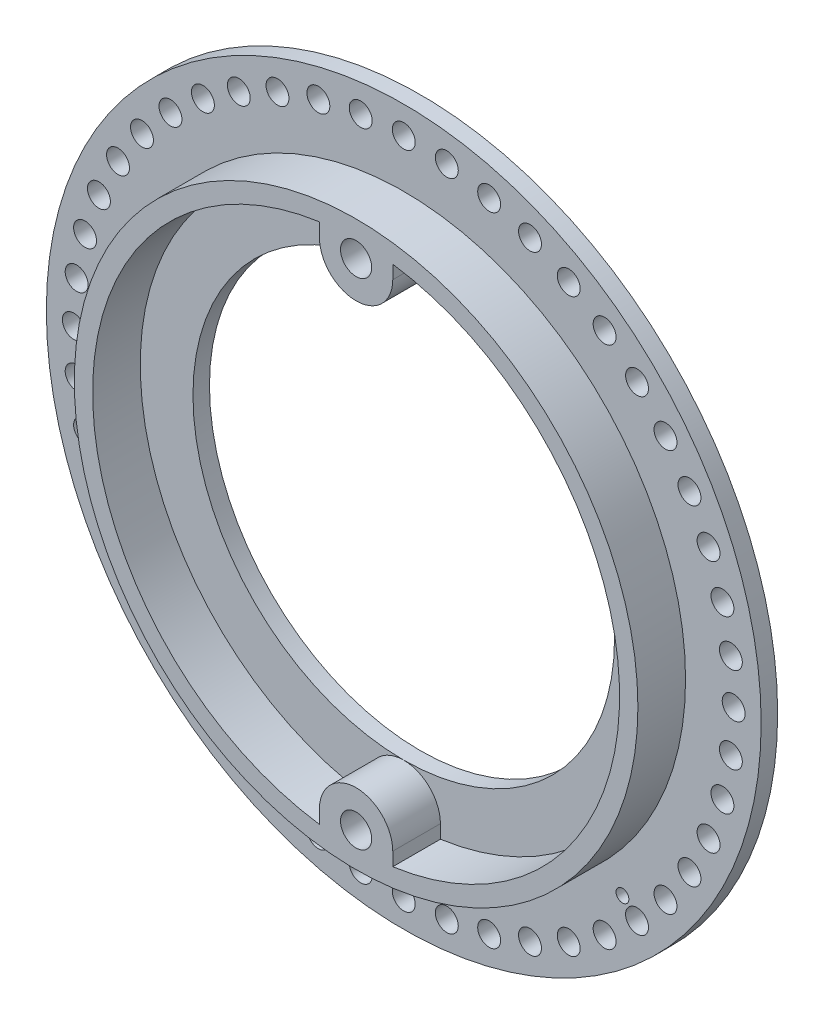
SolidWorks part; units mm, degrees
ref_plane "Front Plane" through (0, 0, 0) normal (0, 0, 1) x (1, 0, 0)
ref_plane "Top Plane" through (0, 0, 0) normal (0, 1, 0) x (1, 0, 0)
ref_plane "Right Plane" through (0, 0, 0) normal (1, 0, 0) x (0, 0, -1)
sketch "Sketch1" plane through (0, 0, 0) normal (0, 0, 1) x (1, 0, 0)
  circle A0 centre (0, 0) radius 39
  dimension "D1" = 78
extrude "Boss-Extrude1" add sketch "Sketch1" along normal blind 1.8
sketch "Sketch3" plane through (0, 0, 1.8) normal (0, 0, 1) x (1, 0, 0)
  line L0 (-4, 27) -> (-4, 28.4704)
  line L1 (4, 27) -> (4, 28.4704)
  line L2 (4, -27) -> (4, -28.4704)
  line L3 (-4, -27) -> (-4, -28.4704)
  circle A0 centre (0, 0) radius 30.75
  arc A1 (-4, 28.4704) -> (-4, -28.4704) centre (0, 0) ccw
  arc A2 (-4, 27) -> (4, 27) centre (0, 27) ccw
  circle A3 centre (0, 0) radius 28.75 construction
  arc A4 (4, -27) -> (-4, -27) centre (0, -27) ccw
  arc A5 (4, -28.4704) -> (4, 28.4704) centre (0, 0) ccw
  point P18 (0, 0)
  point P22 (-0.2453, 0)
  dimension "D1" = 61.5
  dimension "D3" = 8
  dimension "D5" = 2
  dimension "D4" = 27
  dimension "D2" = 2
extrude "Boss-Extrude2" add sketch "Sketch3" along normal blind 5.2 contours A1 L3 A4 L2 A5 L1 A2 L0 | A0
sketch "Sketch5" plane through (0, 0, 7) normal (0, 0, 1) x (1, 0, 0)
  circle A0 centre (0, -27) radius 1.7
  circle A1 centre (0, 27) radius 1.7
  point P7 (0, 0)
  dimension "D1" = 27
  dimension "D2" = 3.4
  dimension "D3" = 2
  dimension "D4" = 54
extrude "Cut-Extrude2" cut sketch "Sketch5" against normal up to surface (7 mm away) up to face at (39, 0, 0)
sketch "Sketch6" plane through (0, 0, 0) normal (0, 0, -1) x (-1, 0, 0)
  circle A0 centre (0, 27) radius 3
  circle A1 centre (0, -27) radius 3
  dimension "D1" = 6
  dimension "D2" = 6
  dimension "D3" = 27
  dimension "D4" = 27
extrude "Cut-Extrude3" cut sketch "Sketch6" against normal blind 4.5
sketch "Sketch7" plane through (0, 0, 0) normal (0, 0, -1) x (-1, 0, 0)
  circle A0 centre (0, 0) radius 23
  dimension "D1" = 46
extrude "Cut-Extrude4" cut sketch "Sketch7" against normal up to surface (1.8 mm away) up to face at (0, 0, 1.8)
sketch "Sketch8" plane through (0, 0, 1.8) normal (0, 0, 1) x (1, 0, 0)
  circle A0 centre (36, 0) radius 1.25
  circle A1 centre (35.692, -4.6989) radius 1.25
  circle A2 centre (34.7733, -9.3175) radius 1.25
  circle A3 centre (33.2597, -13.7766) radius 1.25
  circle A4 centre (31.1769, -18) radius 1.25
  circle A5 centre (28.5607, -21.9154) radius 1.25
  circle A6 centre (25.4558, -25.4558) radius 1.25
  circle A7 centre (21.9154, -28.5607) radius 1.25
  circle A8 centre (18, -31.1769) radius 1.25
  circle A9 centre (13.7766, -33.2597) radius 1.25
  circle A10 centre (9.3175, -34.7733) radius 1.25
  circle A11 centre (4.6989, -35.692) radius 1.25
  circle A12 centre (0, -36) radius 1.25
  circle A13 centre (-4.6989, -35.692) radius 1.25
  circle A14 centre (-9.3175, -34.7733) radius 1.25
  circle A15 centre (-13.7766, -33.2597) radius 1.25
  circle A16 centre (-18, -31.1769) radius 1.25
  circle A17 centre (-21.9154, -28.5607) radius 1.25
  circle A18 centre (-25.4558, -25.4558) radius 1.25
  circle A19 centre (-28.5607, -21.9154) radius 1.25
  circle A20 centre (-31.1769, -18) radius 1.25
  circle A21 centre (-33.2597, -13.7766) radius 1.25
  circle A22 centre (-34.7733, -9.3175) radius 1.25
  circle A23 centre (-35.692, -4.6989) radius 1.25
  circle A24 centre (-36, 0) radius 1.25
  circle A25 centre (-35.692, 4.6989) radius 1.25
  circle A26 centre (-34.7733, 9.3175) radius 1.25
  circle A27 centre (-33.2597, 13.7766) radius 1.25
  circle A28 centre (-31.1769, 18) radius 1.25
  circle A29 centre (-28.5607, 21.9154) radius 1.25
  circle A30 centre (-25.4558, 25.4558) radius 1.25
  circle A31 centre (-21.9154, 28.5607) radius 1.25
  circle A32 centre (-18, 31.1769) radius 1.25
  circle A33 centre (-13.7766, 33.2597) radius 1.25
  circle A34 centre (-9.3175, 34.7733) radius 1.25
  circle A35 centre (-4.6989, 35.692) radius 1.25
  circle A36 centre (0, 36) radius 1.25
  circle A37 centre (4.6989, 35.692) radius 1.25
  circle A38 centre (9.3175, 34.7733) radius 1.25
  circle A39 centre (13.7766, 33.2597) radius 1.25
  circle A40 centre (18, 31.1769) radius 1.25
  circle A41 centre (21.9154, 28.5607) radius 1.25
  circle A42 centre (25.4558, 25.4558) radius 1.25
  circle A43 centre (28.5607, 21.9154) radius 1.25
  circle A44 centre (31.1769, 18) radius 1.25
  circle A45 centre (33.2597, 13.7766) radius 1.25
  circle A46 centre (34.7733, 9.3175) radius 1.25
  circle A47 centre (35.692, 4.6989) radius 1.25
  point P104 (0, 0)
  dimension "D1" = 36
  dimension "D2" = 2.5
  dimension "D3" = 48
extrude "Cut-Extrude5" cut sketch "Sketch8" against normal up to surface (1.8 mm away) up to face at (-23, 0, 0)
fillet "Fillet1" radius 1.5 2 edges at (-3, -27, 4.5) (-3, 27, 4.5)
sketch "Alignment_Hole" plane through (0, 0, 0) normal (0, 0, -1) x (-1, 0, 0)
  line L0 (0, 0) -> (-49.8691, 0) construction
  line L1 (-5.6645, -5.6645) -> (-42.6819, -42.6819) construction
  circle A0 centre (-23.8649, -23.8649) radius 0.7
  circle A1 centre (-25.4558, -25.4558) radius 1.25 construction
  dimension "D1" = 1.4
  dimension "D2" = 2.25
  dimension "D3" = 45
extrude "Alignment_Hole - Cut" cut sketch "Alignment_Hole" against normal through all both and the other way through all
equation "\"D2@Sketch6\"=\"D1@Sketch6\""
